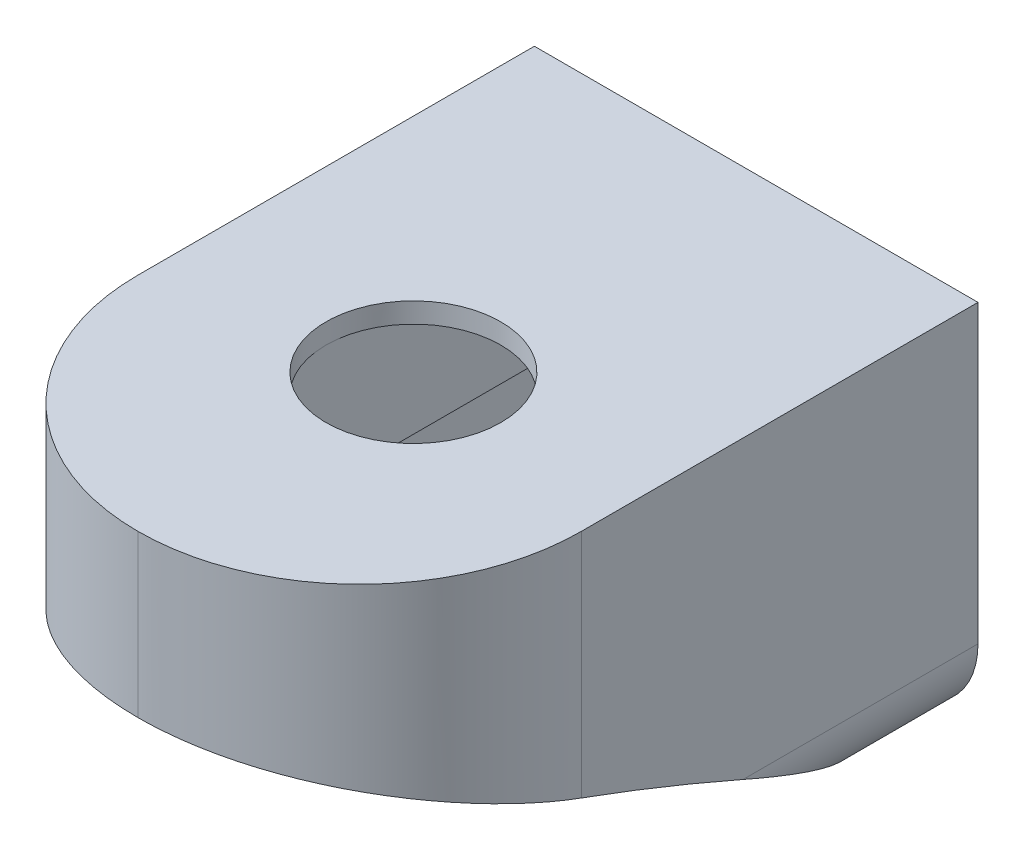
SolidWorks part; units mm, degrees
ref_plane "Front Plane" through (0, 0, 0) normal (0, 0, 1) x (1, 0, 0)
ref_plane "Top Plane" through (0, 0, 0) normal (0, 1, 0) x (1, 0, 0)
ref_plane "Right Plane" through (0, 0, 0) normal (1, 0, 0) x (0, 0, -1)
sketch "Sketch1" plane through (0, 0, 0) normal (0, 0, 1) x (1, 0, 0)
  line L1 (-16.5, 14) -> (16.5, 14)
  line L2 (-16.5, 14) -> (-16.5, -14)
  line L3 (-16.5, -14) -> (16.5, -14)
  line L4 (16.5, 14) -> (16.5, -14)
  line L5 (-16.5, 14) -> (16.5, -14) construction
  line L6 (-16.5, -14) -> (16.5, 14) construction
  point P0 (0, 0)
  dimension "D1" = 33
  dimension "D2" = 28
extrude "Boss-Extrude1" add sketch "Sketch1" along normal blind 46
sketch "Sketch2" plane through (16.5, 0, 0) normal (1, 0, 0) x (0, 0, -1)
  line L0 (-46, -14) -> (0, -14) construction
  line L1 (-46, -14) -> (-46, 14) construction
  line L2 (-46, 2) -> (-46, -14)
  line L3 (-46, -14) -> (-5, -14)
  line L4 (0, -14) -> (0, 14) construction
  line L5 (-46, 14) -> (0, 14) construction
  spline S0 degree 2 poles (-5, -14) (-24.7363, -3.6661) (-46, 2) knots 0 0 0 1 1 1
  dimension "D1" = 5
  dimension "D2" = 12
extrude "Cut-Extrude1" cut sketch "Sketch2" against normal through all
sketch "Sketch3" plane through (16.5, 0, 0) normal (1, 0, 0) x (0, 0, -1)
  line L0 (-5, -14) -> (-2.5, -14)
  line L1 (-5, -14) -> (0, -14) construction
  line L2 (-2.5, -14) -> (-2.5, 3.5)
  line L3 (-2.5, 3.5) -> (-40.5, 3.5)
  line L4 (-40.5, 3.5) -> (-40.5, 0.4487)
  parabola Q0 (-5, -14) -> (-46, 2) focus (-66.0323, -94.5427) apex (-35.4636, -1.1248) construction
  parabola Q1 (-5, -14) -> (-46, 2) focus (-66.0323, -94.5427) apex (-35.4636, -1.1248) construction
  parabola Q2 (-5, -14) -> (-40.5, 0.4487) focus (-66.0323, -94.5427) apex (-35.4636, -1.1248)
  dimension "D1" = 17.5
  dimension "D2" = 38
extrude "Cut-Extrude2" cut sketch "Sketch3" against normal blind 27 from offset 3 offset against normal yes
fillet "Fillet1" radius 12.5 2 edges at (13.5, 1.9744, 40.5) (-13.5, 1.9744, 40.5)
fillet "Fillet2" radius 16.5 2 edges at (16.5, 8, 46) (-16.5, 8, 46)
fillet "Fillet3" radius 6 2 edges at (-16.5, -14, 2.5) (16.5, -14, 2.5)
sketch "Sketch4" plane through (0, 3.5, 0) normal (0, -1, 0) x (1, 0, 0)
  line L0 (0, 0) -> (0, 46) construction
  line L1 (-13.5, 2.5) -> (13.5, 2.5) construction
  line L2 (-6.5, 32) -> (6.5, 32)
  line L3 (-6.5, 32) -> (-6.5, 9)
  line L4 (-6.5, 9) -> (6.5, 9)
  line L5 (6.5, 32) -> (6.5, 9)
  line L6 (-6.5, 32) -> (6.5, 9) construction
  line L7 (-6.5, 9) -> (6.5, 32) construction
  point P4 (0, 20.5)
  dimension "D1" = 6.5
  dimension "D2" = 23
  dimension "D3" = 13
extrude "Cut-Extrude3" cut sketch "Sketch4" against normal blind 9
sketch "Sketch5" plane through (0, 12.5, 0) normal (0, -1, 0) x (1, 0, 0)
  line L0 (0, 9) -> (0, 32) construction
  line L1 (-6.5, 9) -> (6.5, 9) construction
  line L2 (6.5, 32) -> (-6.5, 32) construction
  circle A0 centre (0, 25.5) radius 6.5
  dimension "D1" = 13
extrude "Cut-Extrude4" cut sketch "Sketch5" against normal through all
sketch "Sketch6" plane through (0, 3.5, 0) normal (0, -1, 0) x (1, 0, 0)
  line L0 (-6.5, 20.5) -> (6.5, 20.5) construction
  line L1 (-6.5, 32) -> (-6.5, 9) construction
  line L2 (6.5, 9) -> (6.5, 32) construction
  line L3 (0, 34.3) -> (0, 6.7) construction
  circle A0 centre (0, 34.3) radius 1
  circle A1 centre (0, 6.7) radius 1
  point P10 (0, 20.5)
  dimension "D2" = 2
  dimension "D1" = 27.6
extrude "Cut-Extrude6" cut sketch "Sketch6" against normal blind 8
sketch "Sketch7" plane through (0, 0, 0) normal (0, 0, -1) x (-1, 0, 0)
  line L0 (0, 0) -> (-20.1474, 0) construction
  line L1 (-16.5, -8) -> (-16.5, 14) construction
  circle A0 centre (-9.5, 0) radius 1.3
  circle A1 centre (-5, 0) radius 2.5
  circle A2 centre (-0.5, 0) radius 1.3
  point P11 (-10.3206, 0)
  dimension "D1" = 2.6
  dimension "D2" = 5
  dimension "D3" = 11.5
  dimension "D4" = 9
  dimension "D5" = 4.5
extrude "Cut-Extrude7" cut sketch "Sketch7" against normal up to surface (2.5 mm away) up to face at (0, -7.9645, 2.5)
